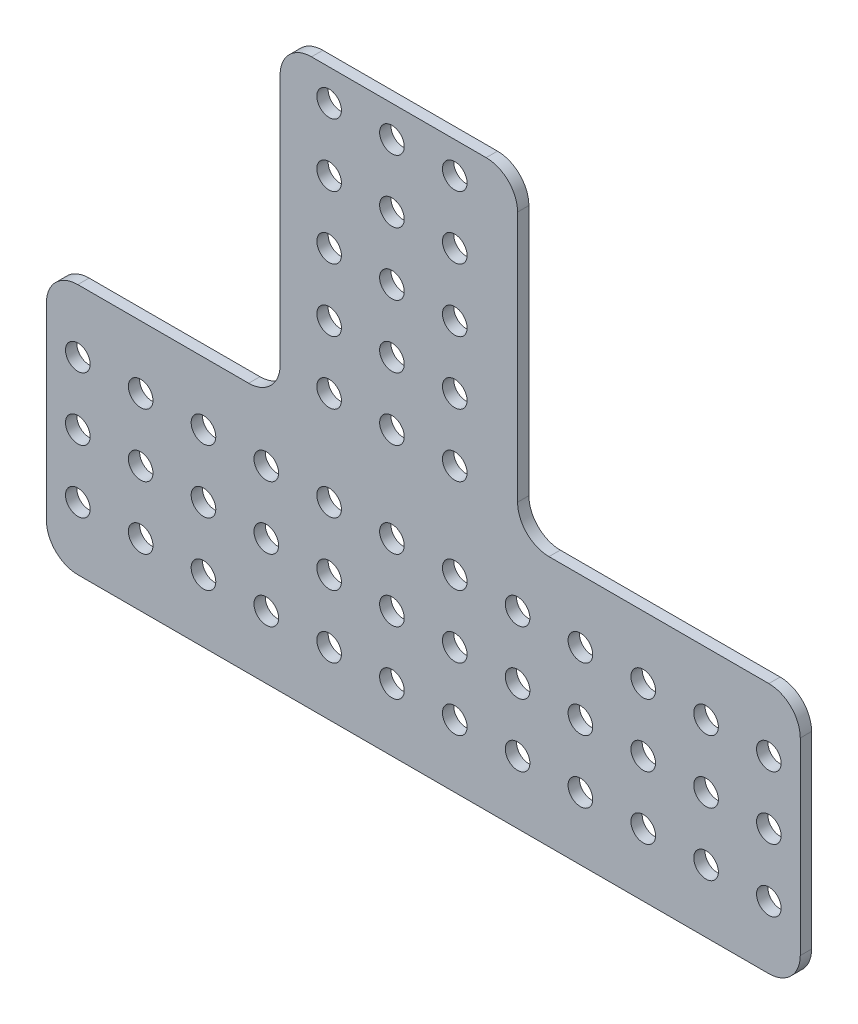
SolidWorks part; units mm, degrees
ref_plane "Front Plane" through (0, 0, 0) normal (0, 0, 1) x (1, 0, 0)
ref_plane "Top Plane" through (0, 0, 0) normal (0, 1, 0) x (1, 0, 0)
ref_plane "Right Plane" through (0, 0, 0) normal (1, 0, 0) x (0, 0, -1)
sketch "Sketch1" plane through (0, 0, 0) normal (0, 0, 1) x (1, 0, 0)
  line L0 (-255.429, 188.8429) -> (-220.1184, 188.8429)
  line L1 (-213.7684, 182.4929) -> (-213.7684, 131.6929)
  line L2 (-207.4184, 125.3429) -> (-162.9684, 125.3429)
  line L3 (-156.6184, 118.9929) -> (-156.6184, 80.8929)
  line L4 (-162.9684, 74.5429) -> (-302.6684, 74.5429)
  line L5 (-309.0184, 80.8929) -> (-309.0184, 118.9929)
  line L6 (-302.6684, 125.3429) -> (-268.129, 125.3429)
  line L7 (-261.779, 131.6929) -> (-261.779, 182.4929)
  line L8 (-264.5684, 125.3429) -> (-213.7684, 125.3429) construction
  line L9 (-213.7684, 811.1429) -> (-213.7684, 125.3429) construction
  line L10 (-302.6684, 112.6429) -> (-289.9684, 112.6429) construction
  line L11 (-302.6684, 112.6429) -> (-302.6684, 99.9429) construction
  line L12 (-226.4684, 131.6929) -> (-226.4684, 112.6429) construction
  arc A0 (-268.129, 125.3429) -> (-261.779, 131.6929) centre (-268.129, 131.6929) ccw
  arc A1 (-309.0184, 118.9929) -> (-302.6684, 125.3429) centre (-302.6684, 118.9929) cw
  arc A2 (-302.6684, 74.5429) -> (-309.0184, 80.8929) centre (-302.6684, 80.8929) cw
  arc A3 (-156.6184, 80.8929) -> (-162.9684, 74.5429) centre (-162.9684, 80.8929) cw
  arc A4 (-162.9684, 125.3429) -> (-156.6184, 118.9929) centre (-162.9684, 118.9929) cw
  arc A5 (-213.7684, 131.6929) -> (-207.4184, 125.3429) centre (-207.4184, 131.6929) ccw
  arc A6 (-255.429, 188.8429) -> (-261.779, 182.4929) centre (-255.429, 182.4929) ccw
  arc A7 (-220.1184, 188.8429) -> (-213.7684, 182.4929) centre (-220.1184, 182.4929) cw
  circle A8 centre (-226.4684, 182.4929) radius 2.4892 construction
  circle A9 centre (-226.4684, 157.0929) radius 2.4892 construction
  circle A10 centre (-226.4684, 144.3929) radius 2.4892 construction
  circle A11 centre (-226.4684, 131.6929) radius 2.4892 construction
  circle A12 centre (-239.1684, 131.6929) radius 2.4892 construction
  circle A13 centre (-251.8684, 131.6929) radius 2.4892 construction
  circle A14 centre (-251.8684, 144.3929) radius 2.4892 construction
  circle A15 centre (-239.1684, 144.3929) radius 2.4892 construction
  circle A16 centre (-239.1684, 157.0929) radius 2.4892 construction
  circle A17 centre (-251.8684, 157.0929) radius 2.4892 construction
  circle A18 centre (-226.4684, 169.7929) radius 2.4892 construction
  circle A19 centre (-239.1684, 182.4929) radius 2.4892 construction
  circle A20 centre (-239.1684, 169.7929) radius 2.4892 construction
  circle A21 centre (-251.8684, 169.7929) radius 2.4892 construction
  circle A22 centre (-251.8684, 182.4929) radius 2.4892 construction
  circle A23 centre (-226.4684, 157.0929) radius 2.4892
  circle A24 centre (-226.4684, 144.3929) radius 2.4892
  circle A25 centre (-226.4684, 131.6929) radius 2.4892
  circle A26 centre (-239.1684, 131.6929) radius 2.4892
  circle A27 centre (-251.8684, 131.6929) radius 2.4892
  circle A28 centre (-251.8684, 144.3929) radius 2.4892
  circle A29 centre (-239.1684, 144.3929) radius 2.4892
  circle A30 centre (-239.1684, 157.0929) radius 2.4892
  circle A31 centre (-251.8684, 157.0929) radius 2.4892
  circle A32 centre (-226.4684, 169.7929) radius 2.4892
  circle A33 centre (-226.4684, 182.4929) radius 2.4892
  circle A34 centre (-239.1684, 182.4929) radius 2.4892
  circle A35 centre (-239.1684, 169.7929) radius 2.4892
  circle A36 centre (-251.8684, 169.7929) radius 2.4892
  circle A37 centre (-251.8684, 182.4929) radius 2.4892
  circle A38 centre (-302.6684, 112.6429) radius 2.4892
  circle A39 centre (-289.9684, 112.6429) radius 2.4892
  circle A40 centre (-277.2684, 112.6429) radius 2.4892
  circle A41 centre (-264.5684, 112.6429) radius 2.4892
  circle A42 centre (-251.8684, 112.6429) radius 2.4892
  circle A43 centre (-239.1684, 112.6429) radius 2.4892
  circle A44 centre (-226.4684, 112.6429) radius 2.4892
  circle A45 centre (-213.7684, 112.6429) radius 2.4892
  circle A46 centre (-201.0684, 112.6429) radius 2.4892
  circle A47 centre (-188.3684, 112.6429) radius 2.4892
  circle A48 centre (-175.6684, 112.6429) radius 2.4892
  circle A49 centre (-162.9684, 112.6429) radius 2.4892
  circle A50 centre (-289.9684, 99.9429) radius 2.4892
  circle A51 centre (-277.2684, 99.9429) radius 2.4892
  circle A52 centre (-264.5684, 99.9429) radius 2.4892
  circle A53 centre (-251.8684, 99.9429) radius 2.4892
  circle A54 centre (-239.1684, 99.9429) radius 2.4892
  circle A55 centre (-226.4684, 99.9429) radius 2.4892
  circle A56 centre (-213.7684, 99.9429) radius 2.4892
  circle A57 centre (-201.0684, 99.9429) radius 2.4892
  circle A58 centre (-188.3684, 99.9429) radius 2.4892
  circle A59 centre (-175.6684, 99.9429) radius 2.4892
  circle A60 centre (-162.9684, 99.9429) radius 2.4892
  circle A61 centre (-289.9684, 87.2429) radius 2.4892
  circle A62 centre (-277.2684, 87.2429) radius 2.4892
  circle A63 centre (-264.5684, 87.2429) radius 2.4892
  circle A64 centre (-251.8684, 87.2429) radius 2.4892
  circle A65 centre (-239.1684, 87.2429) radius 2.4892
  circle A66 centre (-226.4684, 87.2429) radius 2.4892
  circle A67 centre (-213.7684, 87.2429) radius 2.4892
  circle A68 centre (-201.0684, 87.2429) radius 2.4892
  circle A69 centre (-188.3684, 87.2429) radius 2.4892
  circle A70 centre (-175.6684, 87.2429) radius 2.4892
  circle A71 centre (-162.9684, 87.2429) radius 2.4892
  circle A72 centre (-302.6684, 99.9429) radius 2.4892
  circle A73 centre (-302.6684, 87.2429) radius 2.4892
  dimension "D2" = 6.35
  dimension "D6" = 12.7
  dimension "D8" = 4.9784
  dimension "D9" = 12
  dimension "D4" = 6.35
  dimension "D1" = 6.35
  dimension "D3" = 152.4
  dimension "D5" = 50.8
  dimension "D11" = 12.7
  dimension "D12" = 12.7
  dimension "D10" = 3
extrude "Boss-Extrude1" add sketch "Sketch1" along normal blind 2.286
